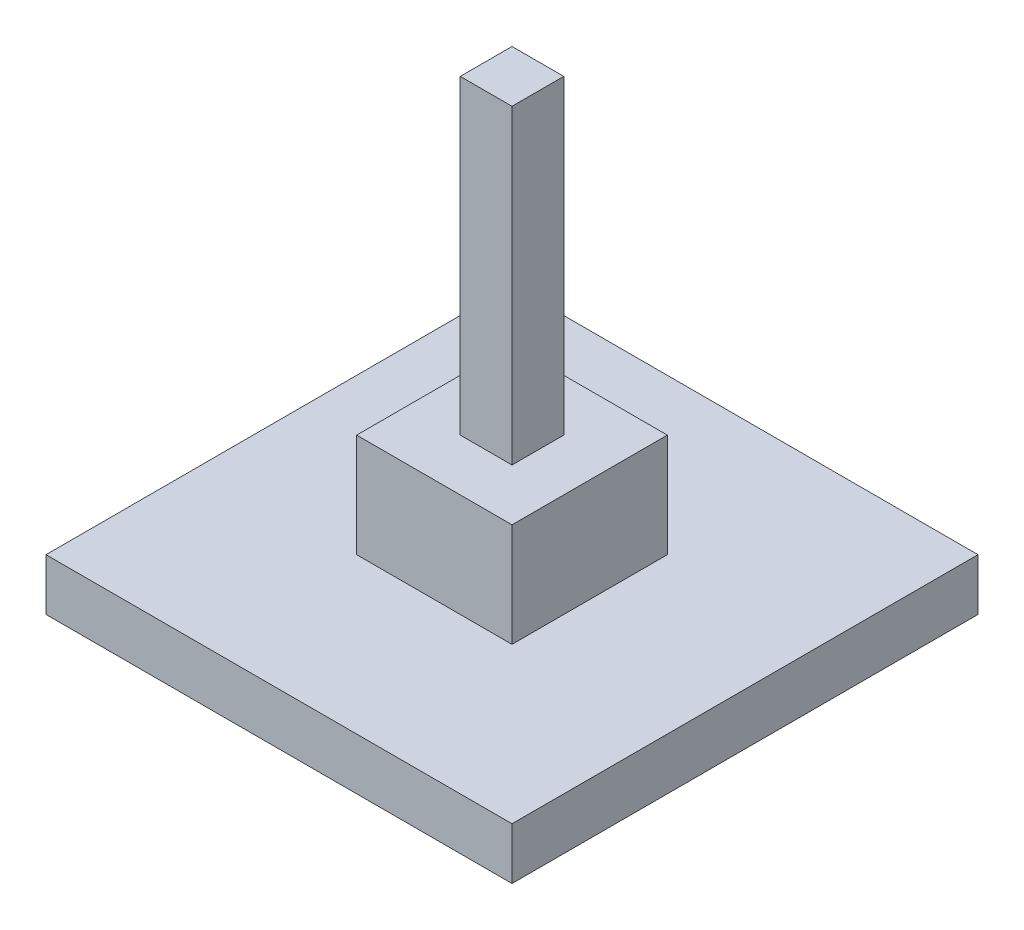
SolidWorks part; units mm, degrees
ref_plane "Front Plane" through (0, 0, 0) normal (0, 0, 1) x (1, 0, 0)
ref_plane "Top Plane" through (0, 0, 0) normal (0, 1, 0) x (1, 0, 0)
ref_plane "Right Plane" through (0, 0, 0) normal (1, 0, 0) x (0, 0, -1)
sketch "Sketch1" plane through (0, 0, 0) normal (0, 1, 0) x (1, 0, 0)
  line L1 (-38.1, -38.1) -> (38.1, -38.1)
  line L2 (-38.1, -38.1) -> (-38.1, 38.1)
  line L3 (-38.1, 38.1) -> (38.1, 38.1)
  line L4 (38.1, -38.1) -> (38.1, 38.1)
  line L5 (-38.1, -38.1) -> (38.1, 38.1) construction
  line L6 (-38.1, 38.1) -> (38.1, -38.1) construction
  line L7 (-114.3, -114.3) -> (114.3, -114.3)
  line L8 (-114.3, -114.3) -> (-114.3, 114.3)
  line L9 (-114.3, 114.3) -> (114.3, 114.3)
  line L10 (114.3, -114.3) -> (114.3, 114.3)
  line L11 (-114.3, -114.3) -> (114.3, 114.3) construction
  line L12 (-114.3, 114.3) -> (114.3, -114.3) construction
  line L13 (-342.9, -342.9) -> (342.9, -342.9)
  line L14 (-342.9, -342.9) -> (-342.9, 342.9)
  line L15 (-342.9, 342.9) -> (342.9, 342.9)
  line L16 (342.9, -342.9) -> (342.9, 342.9)
  line L17 (-342.9, -342.9) -> (342.9, 342.9) construction
  line L18 (-342.9, 342.9) -> (342.9, -342.9) construction
  point P0 (0, 0)
  point P6 (0, 0)
  point P11 (0, 0)
  dimension "D1" = 76.2
  dimension "D2" = 228.6
  dimension "D3" = 685.8
extrude "Boss-Extrude1" add sketch "Sketch1" along normal blind 685.8 contours L1 L4 L3 L2 region at (0, 0, 0)
extrude "Boss-Extrude2" add sketch "Sketch1<3>" along normal blind 228.6 contours L7 L10 L9 L8 L4 L1 L2 L3 region at (-111.0671, 0, 0)
sketch "Sketch1<3>" plane through (0, 0, 0) normal (0, 1, 0) x (1, 0, 0) same geometry as "Sketch1"
extrude "Boss-Extrude3" add sketch "Sketch1<4>" along normal blind 76.2 contours L13 L16 L15 L14 L10 L7 L8 L9 region at (-333.2013, 0, 0)
sketch "Sketch1<4>" plane through (0, 0, 0) normal (0, 1, 0) x (1, 0, 0) same geometry as "Sketch1"
equation "\"A\"= 3"
equation "\"B\"= \"A\" * 3"
equation "\"C\"= \"B\" * \"A\""
equation "\"D1@Sketch1\"=\"A\""
equation "\"D2@Sketch1\"=\"B\""
equation "\"D3@Sketch1\"=\"C\""
equation "\"D1@Boss-Extrude1\"=\"C\""
equation "\"D1@Boss-Extrude2\"=\"B\""
equation "\"D1@Boss-Extrude3\"=\"A\""
